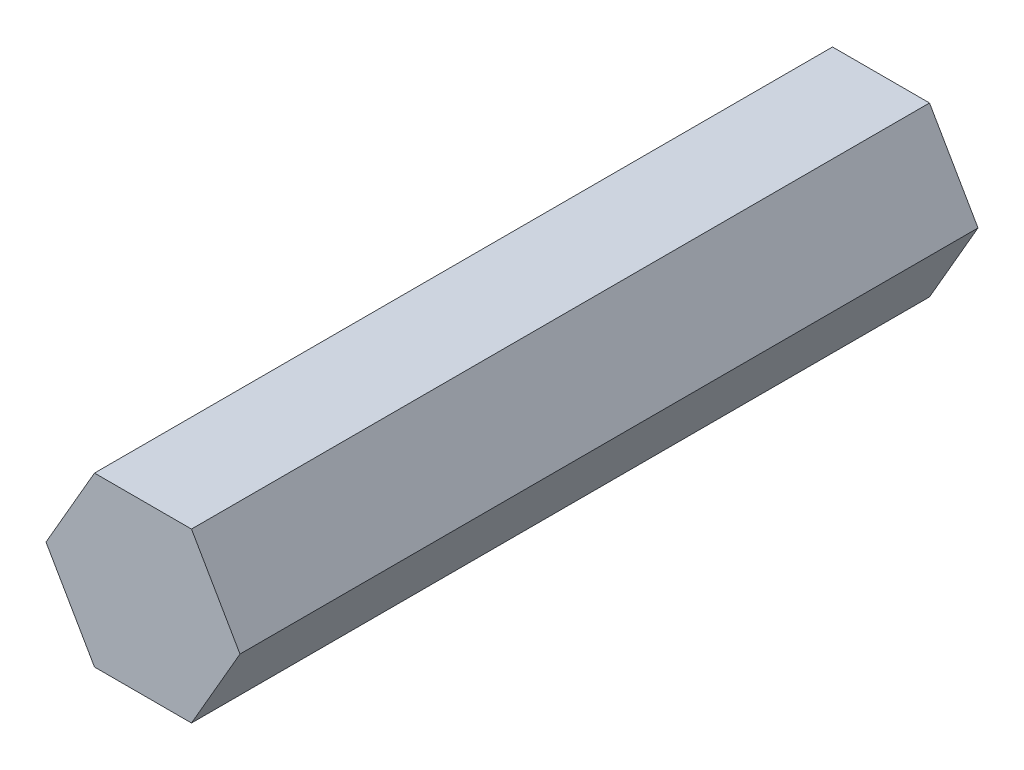
SolidWorks part; units mm, degrees
other "Axis3"
material "Alloy Steel"
ref_plane "Front" through (0, 0, 0) normal (0, 0, 1) x (1, 0, 0)
ref_plane "Top" through (0, 0, 0) normal (0, 1, 0) x (1, 0, 0)
ref_plane "Right" through (0, 0, 0) normal (1, 0, 0) x (0, 0, -1)
sketch "AxisSke" plane through (0, 0, 0) normal (0, 0, 1) x (1, 0, 0)
  line L1 (0.9988, 0) -> (0.4994, 0.865)
  line L2 (0.4994, 0.865) -> (-0.4994, 0.865)
  line L3 (-0.4994, 0.865) -> (-0.9988, 0)
  line L4 (-0.9988, 0) -> (-0.4994, -0.865)
  line L5 (-0.4994, -0.865) -> (0.4994, -0.865)
  line L6 (0.4994, -0.865) -> (0.9988, 0)
  circle A0 centre (0, 0) radius 0.865 construction
  dimension "D1" = 1.73
extrude "Axis" add sketch "AxisSke" along normal blind 7.6
ref_point "Point"
ref_axis "Axis_" through (0, 0, 7.6) along (0, 0, -1)
